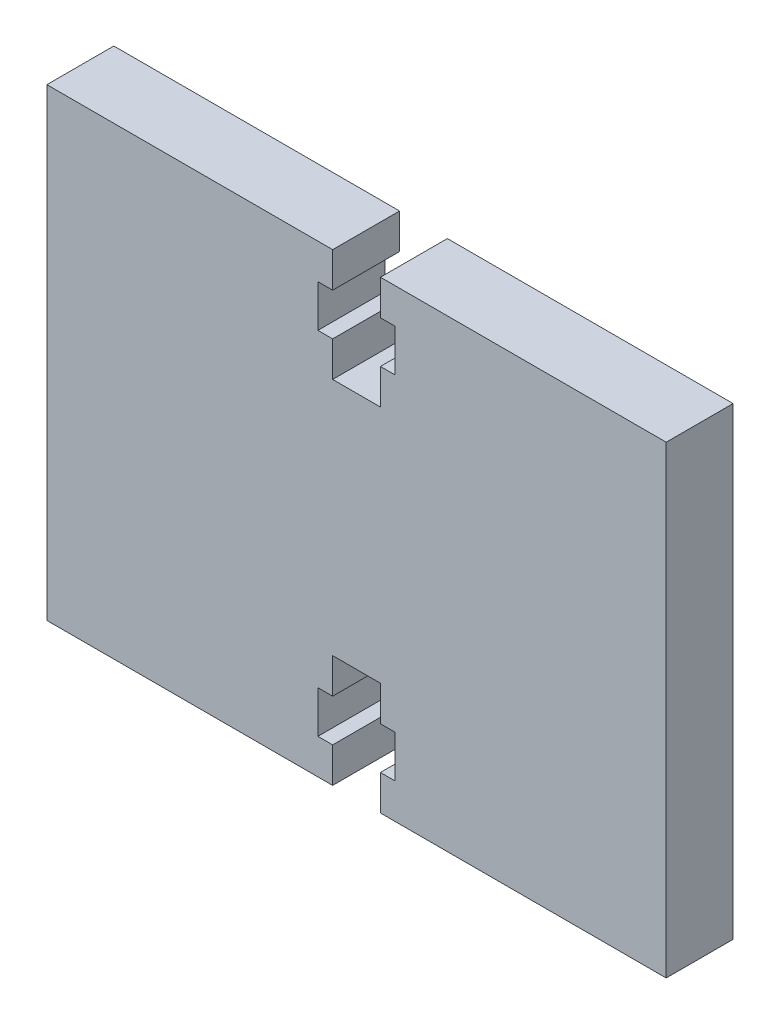
SolidWorks part; units mm, degrees
ref_plane "Front Plane" through (0, 0, 0) normal (0, 0, 1) x (1, 0, 0)
ref_plane "Top Plane" through (0, 0, 0) normal (0, 1, 0) x (1, 0, 0)
ref_plane "Right Plane" through (0, 0, 0) normal (1, 0, 0) x (0, 0, -1)
sketch "Sketch1" plane through (0, 0, 0) normal (0, 0, 1) x (1, 0, 0)
  line L0 (0, 16.51) -> (0, -16.51) construction
  line L1 (-22.0345, -16.51) -> (-1.7, -16.51)
  line L2 (-22.0345, -16.51) -> (-22.0345, 16.51)
  line L3 (-22.0345, 16.51) -> (-1.7, 16.51)
  line L4 (22.0345, -16.51) -> (22.0345, 16.51)
  line L5 (-22.0345, -16.51) -> (22.0345, 16.51) construction
  line L6 (-22.0345, 16.51) -> (22.0345, -16.51) construction
  line L7 (-1.7, 16.51) -> (-1.7, 14.01)
  line L8 (-1.7, 14.01) -> (-2.75, 14.01)
  line L9 (-2.75, 14.01) -> (-2.75, 11.01)
  line L10 (-2.75, 11.01) -> (-1.7, 11.01)
  line L11 (-1.7, 11.01) -> (-1.7, 8.51)
  line L12 (-1.7, 8.51) -> (1.7, 8.51)
  line L13 (-2.75, 12.51) -> (0, 12.51) construction
  line L14 (1.7, 11.01) -> (1.7, 8.51)
  line L15 (2.75, 11.01) -> (1.7, 11.01)
  line L16 (2.75, 14.01) -> (2.75, 11.01)
  line L17 (1.7, 14.01) -> (2.75, 14.01)
  line L18 (1.7, 16.51) -> (1.7, 14.01)
  line L19 (1.7, 16.51) -> (22.0345, 16.51)
  line L20 (0, 0) -> (22.0345, 0) construction
  line L21 (-2.75, -12.51) -> (0, -12.51) construction
  line L22 (1.7, -16.51) -> (1.7, -14.01)
  line L23 (1.7, -14.01) -> (2.75, -14.01)
  line L24 (2.75, -14.01) -> (2.75, -11.01)
  line L25 (2.75, -11.01) -> (1.7, -11.01)
  line L26 (1.7, -11.01) -> (1.7, -8.51)
  line L27 (-1.7, -8.51) -> (1.7, -8.51)
  line L28 (-1.7, -11.01) -> (-1.7, -8.51)
  line L29 (-2.75, -11.01) -> (-1.7, -11.01)
  line L30 (-2.75, -14.01) -> (-2.75, -11.01)
  line L31 (-1.7, -14.01) -> (-2.75, -14.01)
  line L32 (-1.7, -16.51) -> (-1.7, -14.01)
  line L33 (1.7, -16.51) -> (22.0345, -16.51)
  point P0 (0, 0)
  point P18 (0, 8.51)
  point P39 (0, -8.51)
  dimension "D1" = 44.069
  dimension "D2" = 33.02
  dimension "D3" = 8
  dimension "D4" = 3
  dimension "D5" = 4
  dimension "D6" = 2.75
  dimension "D7" = 1.7
extrude "Boss-Extrude1" add sketch "Sketch1" along normal blind 4.7625
equation "\"D5@Sketch1\"=\"D3@Sketch1\"/2"
